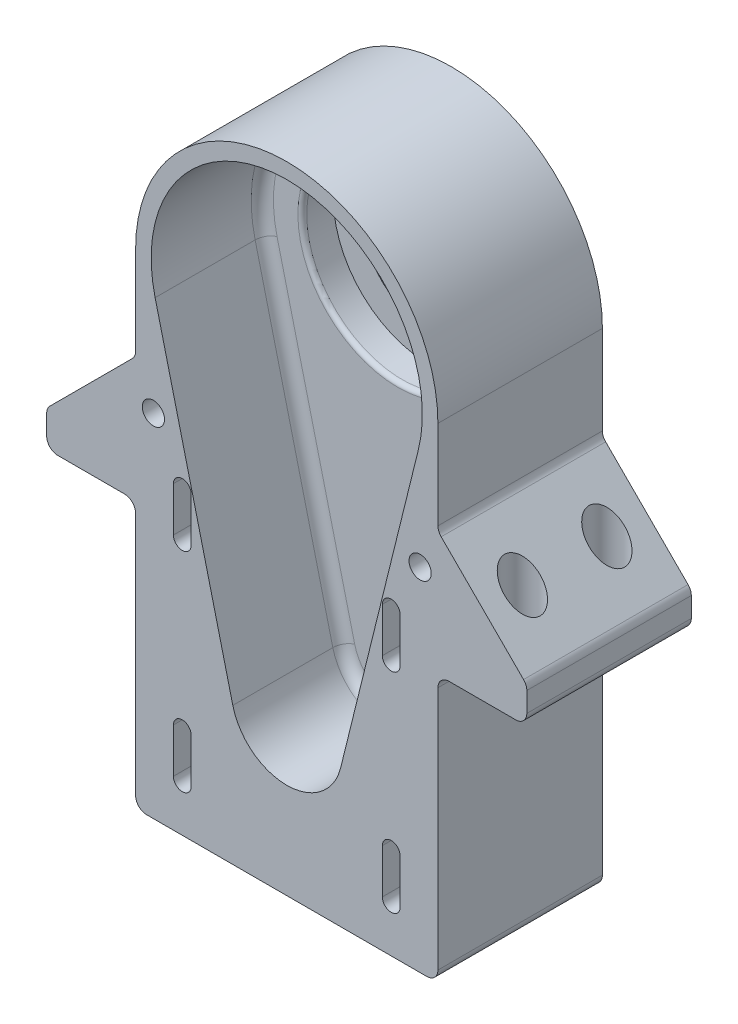
SolidWorks part; units mm, degrees
note: The reader was unsure of these and kept them because the rebuilt part matched: shared geometry of "Esquisse1<7>", "Esquisse1<8>".
ref_plane "Plan de face" through (0, 0, 0) normal (0, 0, 1) x (1, 0, 0)
ref_plane "Plan de dessus" through (0, 0, 0) normal (0, 1, 0) x (1, 0, 0)
ref_plane "Plan de droite" through (0, 0, 0) normal (1, 0, 0) x (0, 0, -1)
sketch "Esquisse1" plane through (0, 0, 0) normal (0, 0, 1) x (1, 0, 0)
  line L0 (0, 0) -> (0, -75) construction
  line L1 (-34, 0) -> (-34, -41)
  line L2 (29, -104) -> (-29, -104)
  line L3 (29, -104) -> (29, -46)
  line L4 (29, -46) -> (-29, -46)
  line L5 (-29, -104) -> (-29, -46)
  line L6 (29, -104) -> (-29, -46) construction
  line L7 (29, -46) -> (-29, -104) construction
  line L8 (23.5, -98.5) -> (-23.5, -98.5)
  line L9 (23.5, -98.5) -> (23.5, -51.5)
  line L10 (23.5, -51.5) -> (-23.5, -51.5)
  line L11 (-23.5, -98.5) -> (-23.5, -51.5)
  line L12 (23.5, -98.5) -> (-23.5, -51.5) construction
  line L13 (23.5, -51.5) -> (-23.5, -98.5) construction
  line L14 (34, -109) -> (-34, -109)
  line L15 (34, -109) -> (34, -41)
  line L16 (34, -41) -> (-34, -41)
  line L17 (-34, -109) -> (-34, -41)
  line L18 (34, -109) -> (-34, -41) construction
  line L19 (34, -41) -> (-34, -109) construction
  line L20 (34, 0) -> (34, -41)
  line L21 (-34, -41) -> (34, -41)
  line L22 (26, 0) -> (34, -41)
  line L23 (-34, -41) -> (-54, -41)
  line L24 (-34, -41) -> (-34, -49)
  line L25 (-34, -49) -> (-54, -49)
  line L26 (-54, -41) -> (-54, -49)
  line L27 (34, -41) -> (54, -41)
  line L28 (34, -41) -> (34, -49)
  line L29 (34, -49) -> (54, -49)
  line L30 (54, -41) -> (54, -49)
  line L31 (-34, -41) -> (-26, 0)
  line L32 (-26, 0) -> (26, 0)
  line L33 (15, 0) -> (18, -75)
  line L34 (18, -75) -> (-18, -75)
  line L35 (-18, -75) -> (-15, 0)
  line L36 (-12.1347, -78) -> (-29.6086, -7.32)
  line L37 (12.1347, -78) -> (29.6086, -7.32)
  line L38 (23.5, -51.5) -> (23.5, -41.5) construction
  line L39 (21.5, -51.5) -> (21.5, -41.5)
  line L40 (25.5, -51.5) -> (25.5, -41.5)
  line L41 (23.5, -98.5) -> (23.5, -88.5) construction
  line L44 (21.5, -98.5) -> (21.5, -88.5)
  line L45 (25.5, -98.5) -> (25.5, -88.5)
  line L46 (-23.5, -51.5) -> (-23.5, -41.5) construction
  line L47 (-21.5, -51.5) -> (-21.5, -41.5)
  line L48 (-25.5, -51.5) -> (-25.5, -41.5)
  line L49 (-23.5, -98.5) -> (-23.5, -88.5) construction
  line L50 (-21.5, -98.5) -> (-21.5, -88.5)
  line L51 (-25.5, -98.5) -> (-25.5, -88.5)
  line L52 (0, -75) -> (0, -65) construction
  line L53 (-18, -75) -> (-18, -65)
  line L54 (18, -75) -> (18, -65)
  line L55 (-54, -41) -> (-34, -21)
  line L56 (54, -41) -> (34, -21)
  circle A0 centre (0, 0) radius 26
  circle A1 centre (0, 0) radius 34
  circle A2 centre (0, -75) radius 18
  circle A3 centre (0, 0) radius 21.5
  circle A4 centre (23.5, -51.5) radius 2
  circle A5 centre (23.5, -98.5) radius 2
  circle A6 centre (-23.5, -98.5) radius 2
  circle A7 centre (-23.5, -51.5) radius 2
  circle A8 centre (0, 0) radius 15
  circle A11 centre (0, 0) radius 30.5
  circle A12 centre (0, -75) radius 12.5
  arc A13 (21.5, -51.5) -> (25.5, -51.5) centre (23.5, -51.5) ccw
  arc A14 (25.5, -41.5) -> (21.5, -41.5) centre (23.5, -41.5) ccw
  arc A17 (21.5, -98.5) -> (25.5, -98.5) centre (23.5, -98.5) ccw
  arc A18 (25.5, -88.5) -> (21.5, -88.5) centre (23.5, -88.5) ccw
  arc A19 (-21.5, -51.5) -> (-25.5, -51.5) centre (-23.5, -51.5) cw
  arc A20 (-25.5, -41.5) -> (-21.5, -41.5) centre (-23.5, -41.5) cw
  arc A21 (-21.5, -98.5) -> (-25.5, -98.5) centre (-23.5, -98.5) cw
  arc A22 (-25.5, -88.5) -> (-21.5, -88.5) centre (-23.5, -88.5) cw
  arc A23 (-18, -75) -> (18, -75) centre (0, -75) ccw
  arc A24 (18, -65) -> (-18, -65) centre (0, -65) ccw
  point P38 (23.5, -46.5)
  point P50 (23.5, -93.5)
  point P57 (-23.5, -46.5)
  point P63 (-23.5, -93.5)
  point P68 (0, -70)
  dimension "D1" = 52
  dimension "D2" = 68
  dimension "D5" = 36
  dimension "D8" = 20
  dimension "D12" = 43
  dimension "D13" = 4
  dimension "D14" = 30
  dimension "D15" = 10
  dimension "D18" = 61
  dimension "D19" = 25
  dimension "D17" = 10
  dimension "D3" = 58
  dimension "D4" = 47
  dimension "D6" = 75
  dimension "D7" = 68
  dimension "D9" = 20
  dimension "D10" = 8
  dimension "D11" = 8
  dimension "D16" = 10
  dimension "D20" = 45
  dimension "D21" = 45
extrude "Boss.-Extru.1" add sketch "Esquisse1" along normal blind 32 contours A11 L37 L22 A1 L31 L36 | A1 L1 L31 | L21 A20 L36 A1 L31 | A1 L22 L20 | A14 L16 L22 A1 L37 | L37 A1 L22 | L31 A1 L36 | L48 A20 L21 L17 L14 L15 L16 A14 L40 L4 L3 L2 L5 | L21 A20 L47 L4 L36 | A14 L16 L37 L4 L39 | L10 L39 L4 L37 | L51 A22 L11 A7 L48 L4 L5 L2 L3 L40 A4 L9 A18 L45 A5 L8 A6 | L47 L10 L36 L4 | A24 L54 A2 L53 L35 L36 L10 A7 L11 A22 L50 L8 L44 A18 L9 A4 L37 L33 | L35 A24 L53 A2 | L54 A24 L33 A2 | A24 L33 L37 | L33 A24 L37 A2 | L33 A2 L37 L34 | A12 L36 L34 A2 L37 | A24 L36 L35 | L36 A24 L35 A2 | L36 A2 L35 L34 | L33 A2 | L35 A2 | L55 L23 L1 | L23 L26 L25 L17 | L30 L27 L15 L29 | L27 L56 L20
extrude "Boss.-Extru.3" add sketch "Esquisse1<7>" against normal blind 5
sketch "Esquisse1<7>" plane through (0, 0, 0) normal (0, 0, 1) x (1, 0, 0) same geometry as "Esquisse1"
extrude "Boss.-Extru.4" add sketch "Esquisse1<8>" along normal blind 7 contours A11 L31 A0 L22 | L31 A11 L35 A0 | L35 A11 L33 A0 | L33 A11 L22 A0 | A11 L33 A1 L37 L22 | A11 L35 A1 L33 | A11 L31 L36 A1 L35 | A1 L36 L16 L35 | A1 L35 L21 L33 | A1 L33 L21 L37 | A11 L22 L37 | A11 L36 L31 | L36 L4 L35 L16 | L35 L4 L33 L21 | L4 L37 L21 L33 | L10 L37 L4 L33 | L35 L10 L33 L4 | L36 L10 L35 L4 | L36 L35 L10 | A2 L37 L33 L10 L35 L36 | L33 L37 L10 | A12 L34 L37 A2 L36 | L34 A12 | L34 A12 | A12 L34 L36 | A12 L37 L34 | A24 L10 L35 L36 | L10 A24 | A24 L37 L33 L10 | A3 L32 A0 | A3 L32 A0 L35 | A3 L33 A0 L32 | A3 L35 A0 L33
sketch "Esquisse1<8>" plane through (0, 0, 0) normal (0, 0, 1) x (1, 0, 0) same geometry as "Esquisse1"
fillet "Congé2" radius 1 1 edges at (21.5, 0, 7)
fillet "Congé3" radius 2.5 4 edges at (20.8716, -42.66, 7) (0, -87.5, 7) (0, 30.5, 7) (-20.8716, -42.66, 7)
sketch "Esquisse2" plane through (0, 0, -5) normal (0, 0, -1) x (-1, 0, 0)
  line L0 (0, 0) -> (0, -51.9425) construction
  circle A0 centre (-30, -30) radius 2.5
  circle A1 centre (30, -30) radius 2.5
  dimension "D3" = 5
  dimension "D1" = 30
  dimension "D2" = 30
extrude "Enlèv. mat.-Extru.1" cut sketch "Esquisse2" against normal through all contours A1 | A0
fillet "Congé4" radius 2.5 10 edges at (-34, -21, 13.5) (-54, -41, 13.5) (-54, -49, 13.5) (-34, -49, 13.5) (-34, -109, 13.5) (34, -109, 13.5) (34, -49, 13.5) (54, -49, 13.5) (54, -41, 13.5) (34, -21, 13.5)
sketch "Esquisse3" plane through (0, -49, 0) normal (0, -1, 0) x (1, 0, 0)
  line L0 (-54, 32) -> (-54, -5) construction
  line L1 (-54, 13.5) -> (54, 13.5) construction
  line L2 (54, -5) -> (54, 32) construction
  line L3 (0, -5) -> (0, 32) construction
  line L4 (-34, -5) -> (34, -5) construction
  line L5 (34, 32) -> (-34, 32) construction
  line L6 (-53.2678, -5) -> (-34.7322, -5) construction
  circle A0 centre (-44, 4) radius 4
  circle A1 centre (44, 4) radius 4
  circle A2 centre (44, 23) radius 4
  circle A3 centre (-44, 23) radius 4
  dimension "D1" = 8
  dimension "D2" = 10
  dimension "D3" = 9
extrude "Enlèv. mat.-Extru.2" cut sketch "Esquisse3" against normal through all
